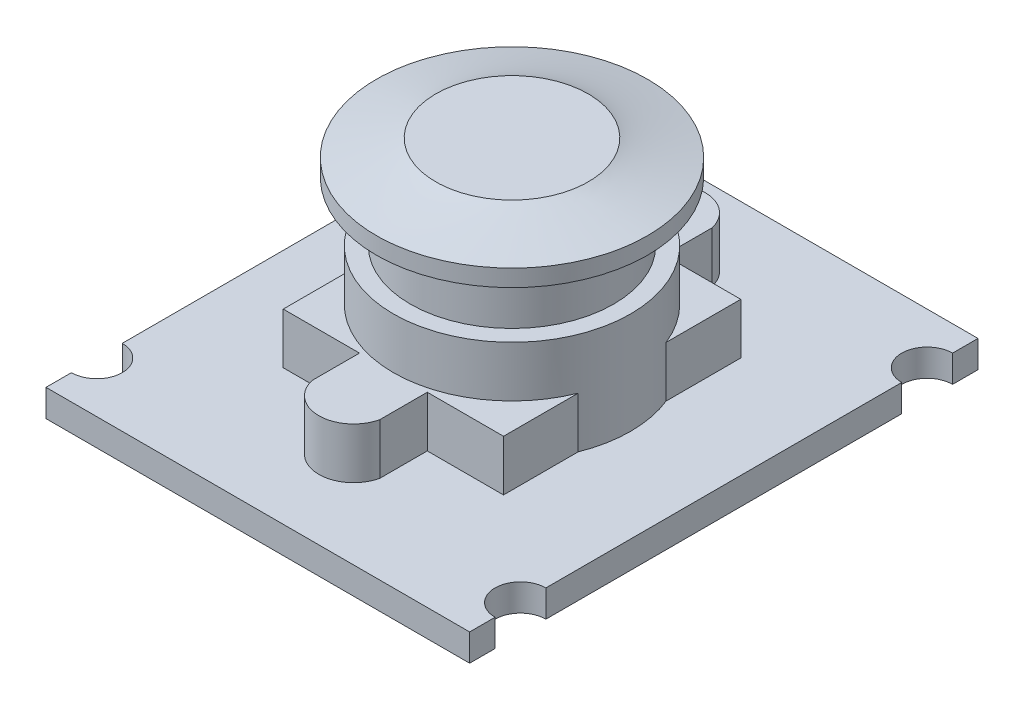
SolidWorks part; units mm, degrees
ref_plane "Front" through (0, 0, 0) normal (0, 0, 1) x (1, 0, 0)
ref_plane "Top" through (0, 0, 0) normal (0, 1, 0) x (1, 0, 0)
ref_plane "Right" through (0, 0, 0) normal (1, 0, 0) x (0, 0, -1)
sketch "Sketch1" plane through (0, 0, 0) normal (0, 1, 0) x (1, 0, 0)
  line L1 (-12.5, -15) -> (12.5, -15)
  line L2 (-12.5, -15) -> (-12.5, 15)
  line L3 (-12.5, 15) -> (12.5, 15)
  line L4 (12.5, -15) -> (12.5, 15)
  line L5 (-12.5, -15) -> (12.5, 15) construction
  line L6 (-12.5, 15) -> (12.5, -15) construction
  point P0 (0, 0)
  dimension "D1" = 25
  dimension "D2" = 30
extrude "Boss-Extrude1" add sketch "Sketch1" along normal blind 1.6
sketch "Sketch2" plane through (0, 1.6, 0) normal (0, 1, 0) x (1, 0, 0)
  line L0 (0, -15) -> (0, -11.4) construction
  line L1 (-12.5, -15) -> (12.5, -15) construction
  line L2 (0, -11.4) -> (0, -9.8) construction
  line L3 (0, -9.8) -> (-2, -9.8) construction
  line L4 (-2, -9.8) -> (2, -9.8) construction
  line L5 (2, -9.8) -> (2, -7)
  line L6 (2, -15) -> (2, -7) construction
  line L7 (2, -7) -> (0, -7) construction
  line L8 (0, -7) -> (6.5, -7) construction
  line L9 (2, -7) -> (6.5, -7)
  line L10 (6.5, -7) -> (6.5, 7)
  line L11 (0, -11.4) -> (0, 0) construction
  line L12 (-6.5, -7) -> (-6.5, 7)
  line L13 (-2, -7) -> (-6.5, -7)
  line L14 (-2, -9.8) -> (-2, -7)
  line L15 (-6.5, 0) -> (6.5, 0) construction
  line L16 (2, 7) -> (6.5, 7)
  line L17 (2, 9.8) -> (2, 7)
  line L18 (-2, 9.8) -> (-2, 7)
  line L19 (-2, 7) -> (-6.5, 7)
  arc A0 (-2, -9.8) -> (2, -9.8) centre (0, -9.35) ccw
  arc A1 (-2, 9.8) -> (2, 9.8) centre (0, 9.35) cw
  dimension "D5" = 2.05
  dimension "D1" = 5.2
  dimension "D4" = 4
  dimension "D6" = 8
  dimension "D7" = 2
  dimension "D8" = 6.5
  dimension "D9" = 7
extrude "Boss-Extrude2" add sketch "Sketch2" along normal blind 3
sketch "Sketch3" plane through (0, 4.6, 0) normal (0, 1, 0) x (1, 0, 0)
  circle A0 centre (0, 0) radius 7
  dimension "D1" = 14
extrude "Boss-Extrude3" add sketch "Sketch3" against normal blind 3
sketch "Sketch4" plane through (0, 4.6, 0) normal (0, 1, 0) x (1, 0, 0)
  circle A0 centre (0, 0) radius 7
  dimension "D1" = 14
extrude "Boss-Extrude4" add sketch "Sketch4" along normal blind 3
sketch "Sketch5" plane through (0, 7.6, 0) normal (0, 1, 0) x (1, 0, 0)
  circle A0 centre (0, 0) radius 6
  dimension "D1" = 12
extrude "Boss-Extrude5" add sketch "Sketch5" along normal blind 3.5
sketch "Sketch6" plane through (0, 11.1, 0) normal (0, 1, 0) x (1, 0, 0)
  circle A0 centre (0, 0) radius 8
  dimension "D1" = 16
extrude "Boss-Extrude6" add sketch "Sketch6" along normal blind 1
sketch "Sketch8" plane through (0, 12.1, 0) normal (0, 1, 0) x (1, 0, 0)
  circle A0 centre (0, 0) radius 8
ref_plane "Plane1" through (0, 13.1, 0) normal (0, 1, 0) x (1, 0, 0)
sketch "Sketch9" plane through (0, 13.1, 0) normal (0, 1, 0) x (1, 0, 0)
  circle A0 centre (0, 0) radius 4.5
  dimension "D1" = 9
loft "Loft1" add profiles "Sketch8", "Sketch9" connector at (-7.2933, 12.1, -3.2875) connector at (-4.4579, 13.1, 0.6145)
sketch "Sketch10" plane through (0, 1.6, 0) normal (0, 1, 0) x (1, 0, 0)
  line L0 (12.5, -15) -> (12.5, -12) construction
  line L1 (12.5, -15) -> (12.5, 15) construction
  circle A0 centre (12.5, -12) radius 1.5
  dimension "D2" = 3
  dimension "D1" = 3
extrude "Cut-Extrude1" cut sketch "Sketch10" against normal blind 2
ref_plane "Plane2" through (0, 0, 0) normal (-1, 0, 0) x (0, 0, 1)
mirror "Mirror1" about plane through (0, 0, 0) normal (-1, 0, 0) of "Cut-Extrude1"
ref_plane "Plane3" through (0, 0, 0) normal (0, 0, 1) x (1, 0, 0)
mirror "Mirror2" about plane through (0, 0, 0) normal (0, 0, 1) of "Mirror1"
sketch "Sketch11" plane through (0, 0, 0) normal (0, -1, 0) x (-1, 0, 0)
  line L0 (12.5, 15) -> (12.5, 9.2) construction
  line L1 (12.5, 10.5) -> (12.5, -10.5) construction
  line L2 (12.5, 9.2) -> (8.1, 9.2)
  line L3 (8.1, 9.2) -> (8.1, 1.8)
  line L4 (8.1, 1.8) -> (12.5, 1.8)
  line L5 (12.5, 1.8) -> (12.5, 9.2)
  dimension "D1" = 5.8
  dimension "D2" = 4.4
  dimension "D3" = 7.4
extrude "Boss-Extrude7" add sketch "Sketch11" along normal blind 3.2
sketch "Sketch12" plane through (-12.5, 0, 0) normal (-1, 0, 0) x (0, 0, 1)
  line L0 (-9.2, -3.2) -> (-8.4, -3.2) construction
  line L1 (-1.8, -3.2) -> (-9.2, -3.2) construction
  line L2 (-8.4, -3.2) -> (-8.4, -2.7) construction
  line L3 (-5.5, -3.2) -> (-5.5, 0) construction
  line L4 (-5.5, 0) -> (-9.2, 0) construction
  line L5 (-8.4, -2.7) -> (-2.6, -2.7)
  line L6 (-8.4, -3.2) -> (-8.4, -2.4) construction
  line L7 (-8.4, -2.7) -> (-8.4, -2.4)
  line L8 (-8.4, -2.4) -> (-8.5, -2.4)
  line L9 (-8.5, -2.4) -> (-8.5, -1.9)
  line L10 (-8.5, -1.9) -> (-8.4, -1.9)
  line L11 (-8.4, 0) -> (-8.4, -0.5) construction
  line L12 (-8.4, -1.9) -> (-8.4, -0.5)
  line L13 (-8.4, -0.5) -> (-2.6, -0.5)
  line L14 (-2.6, -1.9) -> (-2.6, -0.5)
  line L15 (-2.5, -1.9) -> (-2.6, -1.9)
  line L16 (-2.5, -2.4) -> (-2.5, -1.9)
  line L17 (-2.6, -2.4) -> (-2.5, -2.4)
  line L18 (-2.6, -2.7) -> (-2.6, -2.4)
  point P19 (-5.5, -0.5)
  point P24 (-5.5, -2.7)
  dimension "D1" = 0.8
  dimension "D2" = 0.5
  dimension "D3" = 0.8
  dimension "D4" = 0.1
  dimension "D5" = 0.5
  dimension "D6" = 0.1
  dimension "D7" = 0.5
extrude "Cut-Extrude2" cut sketch "Sketch12" against normal blind 3
sketch "Sketch13" plane through (-12.5, 0, 0) normal (-1, 0, 0) x (0, 0, 1)
  line L0 (-9.2, 0) -> (-1.8, 0)
  line L1 (-9.2, 0) -> (-9.2, -0.01)
  line L2 (-9.2, -3.2) -> (-9.2, 0) construction
  line L3 (-9.2, -0.01) -> (-1.8, -0.01)
  line L4 (-1.8, -3.2) -> (-1.8, 0) construction
  line L5 (-1.8, -0.01) -> (-1.8, 0)
  dimension "D1" = 0.01
extrude "Cut-Extrude3" cut sketch "Sketch13" against normal blind 3
